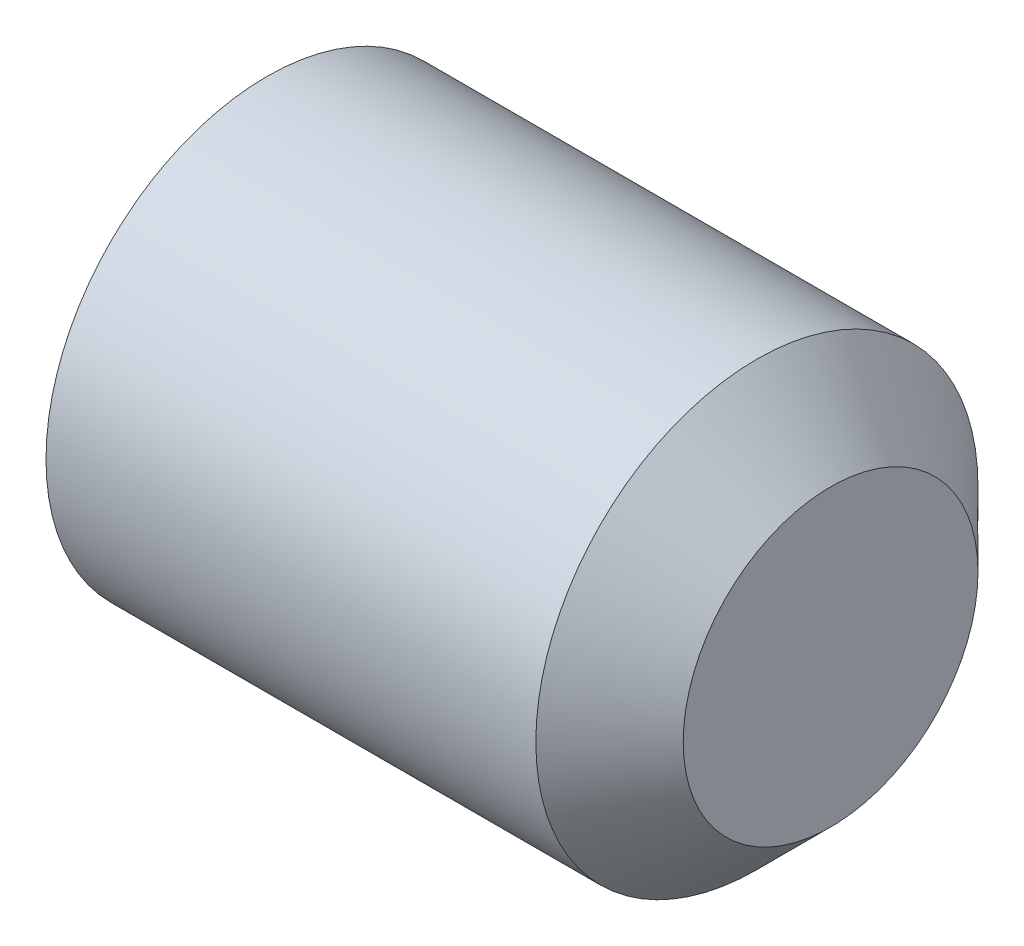
SolidWorks part; units mm, degrees
ref_plane "Front Plane" through (0, 0, 0) normal (0, 0, 1) x (1, 0, 0)
ref_plane "Top Plane" through (0, 0, 0) normal (0, 1, 0) x (1, 0, 0)
ref_plane "Right Plane" through (0, 0, 0) normal (1, 0, 0) x (0, 0, -1)
ref_plane "Plane1" through (-4, 0, 0) normal (1, 0, 0) x (0, 0, -1)
sketch "Sketch1" plane through (0, 0, 0) normal (0, 0, 1) x (1, 0, 0)
  line L0 (-4, 0) -> (0, 0) construction
  line L1 (0, 0) -> (0, 1)
  line L2 (-0.5, 1.5) -> (-3.8233, 1.5)
  line L3 (-4, 1.194) -> (-4, 0)
  line L4 (-4, 0) -> (0, 0)
  line L5 (0, 1) -> (-0.5, 1.5)
  line L6 (-4, 1.194) -> (-3.8233, 1.5)
  point P4 (0, -1)
  point P6 (-3.8233, -1.5)
  point P11 (-4, -1.194)
  dimension "FIX_1" = 60
  dimension "FIX_2" = 45
  dimension "MSM_21" = 2
  dimension "L_1" = 4
  dimension "M_1" = 3
  dimension "KSS_1" = 2.388
revolve "Revolve1" add sketch "Sketch1" angle 360 about L0
cosmetic thread "Thread401" parameters "ATD"=2.459
sketch "Sketch2" plane through (-4, 0, 0) normal (1, 0, 0) x (0, 0, -1)
  line L1 (0.75, -0.433) -> (0.75, 0.433)
  line L2 (0.75, 0.433) -> (0, 0.866)
  line L3 (0, 0.866) -> (-0.75, 0.433)
  line L4 (-0.75, 0.433) -> (-0.75, -0.433)
  line L5 (-0.75, -0.433) -> (0, -0.866)
  line L6 (0, -0.866) -> (0.75, -0.433)
  circle A0 centre (0, 0) radius 0.75 construction
  dimension "MSM_23" = 1.5
extrude "Cut-Extrude1" cut sketch "Sketch2" along normal blind 1.2
equation "\"KSS_1\"= IIF ( ( \"M_1\" = 4 ) , 3.142 , IIF ( ( \"M_1\" = 3 ) , 2.388 , 4.02 ) )"
